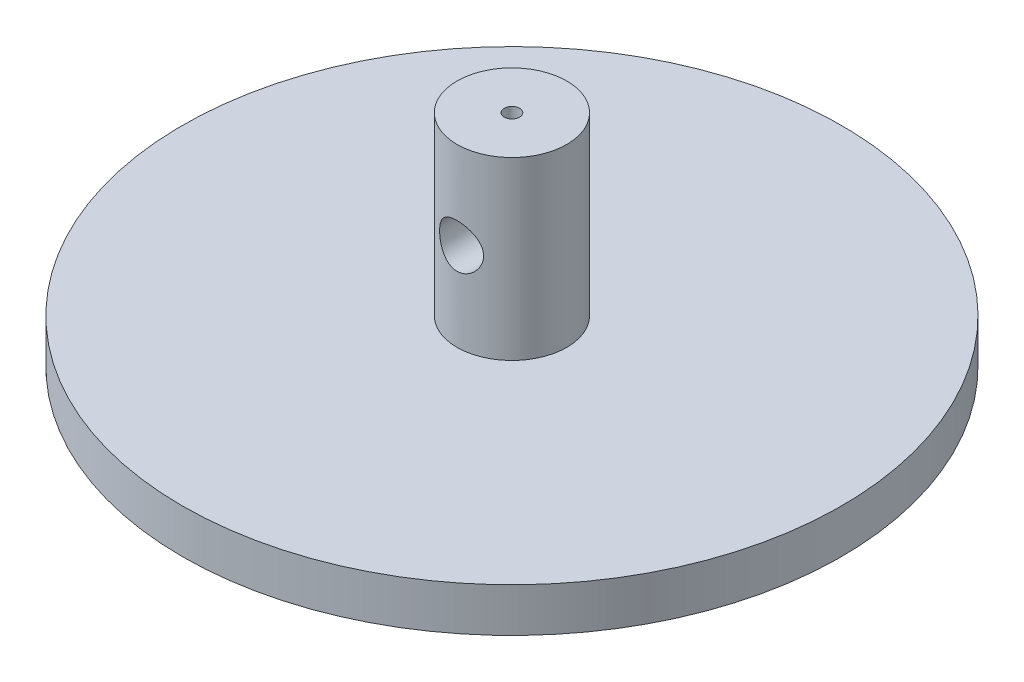
SolidWorks part; units mm, degrees
ref_plane "前视基准面" through (0, 0, 0) normal (0, 0, 1) x (1, 0, 0)
ref_plane "上视基准面" through (0, 0, 0) normal (0, 1, 0) x (1, 0, 0)
ref_plane "右视基准面" through (0, 0, 0) normal (1, 0, 0) x (0, 0, -1)
other "Configuration Table"
sketch "草图1" plane through (0, 0, 0) normal (0, 1, 0) x (1, 0, 0)
  circle A0 centre (0, 0) radius 2.5
  circle A1 centre (0, 0) radius 15
  dimension "D3" = 5
  dimension "D1" = 30
extrude "凸台-拉伸1" add sketch "草图1" along normal blind 2 contours A1
extrude "凸台-拉伸2" add sketch "草图1<7>" along normal blind 10 contours A0
sketch "草图1<7>" plane through (0, 0, 0) normal (0, 1, 0) x (1, 0, 0) same geometry as "草图1"
sketch "草图2" plane through (0, 10, 0) normal (0, 1, 0) x (1, 0, 0)
  circle A0 centre (0, 0) radius 0.35
  dimension "D1" = 0.7
extrude "切除-拉伸1" cut sketch "草图2" against normal blind 4
sketch "草图3" plane through (0, 0, 0) normal (0, 0, 1) x (1, 0, 0)
  line L0 (-2.5, 6) -> (2.5, 6) construction
  line L1 (-2.5, 10) -> (-2.5, 2) construction
  line L2 (2.5, 2) -> (2.5, 10) construction
  circle A0 centre (0, 6) radius 1
  point P8 (0, 0)
  dimension "D1" = 2
extrude "切除-拉伸3" cut sketch "草图3" against normal through all both and the other way through all
